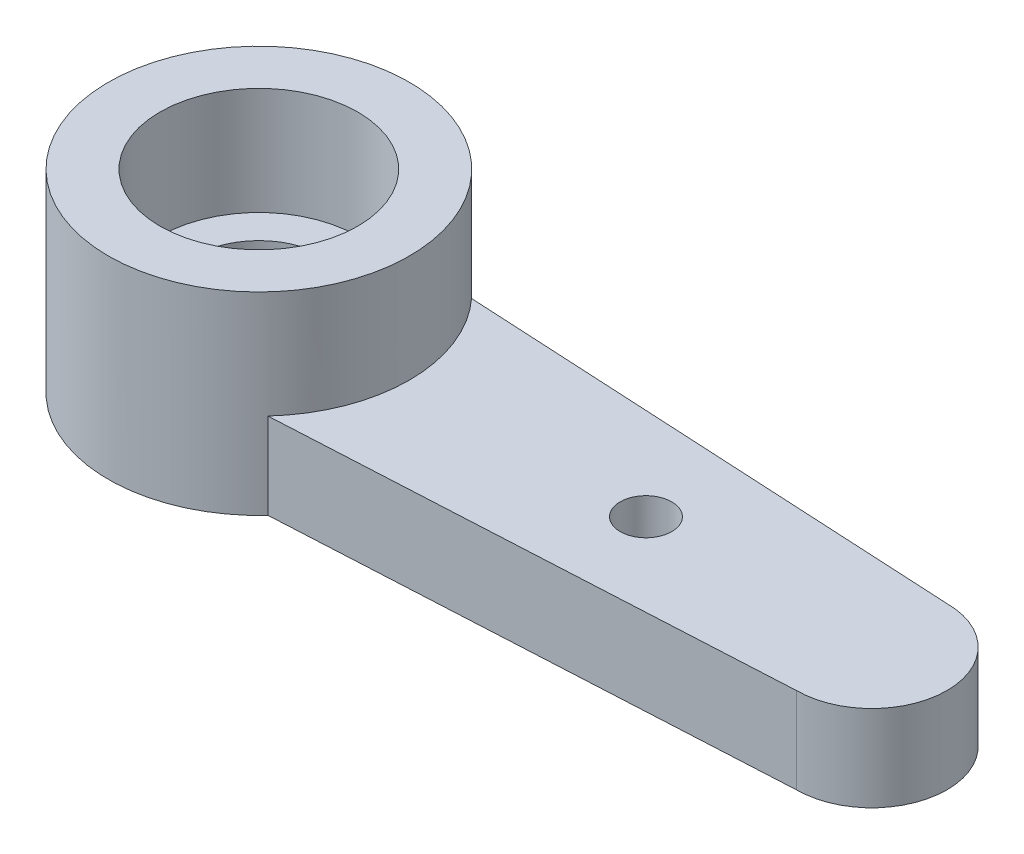
SolidWorks part; units mm, degrees
material "PVC 0.007 Plasticized"
ref_plane "Front Plane" through (0, 0, 0) normal (0, 0, 1) x (1, 0, 0)
ref_plane "Top Plane" through (0, 0, 0) normal (0, 1, 0) x (1, 0, 0)
ref_plane "Right Plane" through (0, 0, 0) normal (1, 0, 0) x (0, 0, -1)
sketch "Sketch1" plane through (0, 0, 0) normal (0, 1, 0) x (1, 0, 0)
  line L0 (14.25, 1.75) -> (2.5781, 2.3672)
  line L1 (14.25, -1.75) -> (2.5781, -2.3672)
  circle A0 centre (0, 0) radius 2.3
  circle A1 centre (0, 0) radius 3.5
  arc A2 (14.25, -1.75) -> (14.25, 1.75) centre (14.25, 0) ccw
  circle A3 centre (0, 0) radius 2.5 construction
  dimension "D1" = 4.6
  dimension "D2" = 7
  dimension "D3" = 3.5
  dimension "D5" = 5
  dimension "D4" = 14.25
extrude "Boss-Extrude1" add sketch "Sketch1" along normal blind 2.5 contours A1 A0 region at (3.1691, 0, -1.2343)
extrude "Boss-Extrude2" add sketch "Sketch1<3>" against normal blind 2 contours A1 A0 | L1 A2 L0 A1 region at (9.0958, 0, 0) region at (3.1691, 0, -1.2343)
sketch "Sketch1<3>" plane through (0, 0, 0) normal (0, 1, 0) x (1, 0, 0) same geometry as "Sketch1"
sketch "Sketch2" plane through (0, 0, 0) normal (0, 1, 0) x (1, 0, 0)
  circle A0 centre (0, 0) radius 1.5
  circle A1 centre (0, 0) radius 2.3 construction
  circle A2 centre (0, 0) radius 2.3
  dimension "D1" = 3
extrude "Boss-Extrude3" add sketch "Sketch2" against normal blind 1
sketch "Sketch3" plane through (0, -2, 0) normal (0, -1, 0) x (1, 0, 0)
  circle A0 centre (9, 0) radius 0.6
  point P2 (0, 0)
  dimension "D2" = 1.2
  dimension "D1" = 9
extrude "Cut-Extrude1" cut sketch "Sketch3" against normal blind 10
